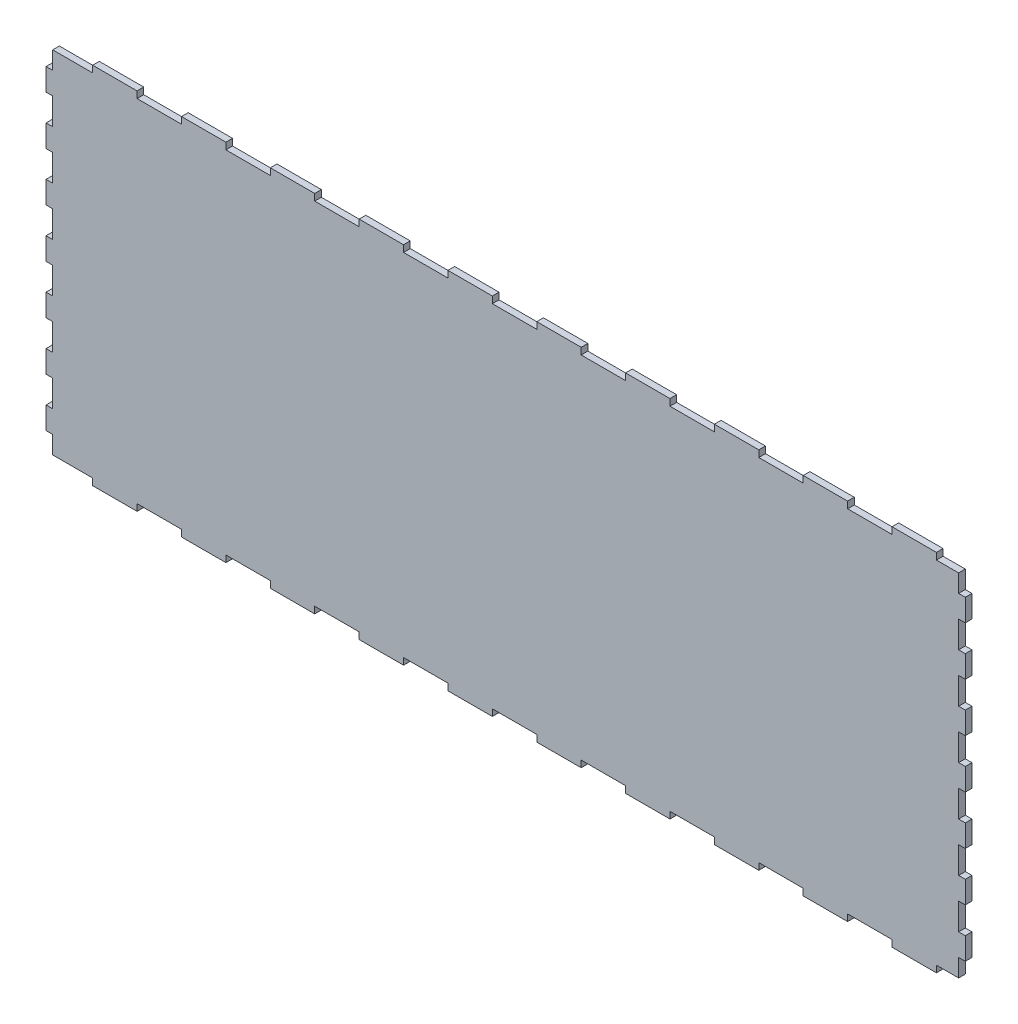
SolidWorks part; units mm, degrees
material "birch 3mm plywood"
ref_plane "Front Plane" through (0, 0, 0) normal (0, 0, 1) x (1, 0, 0)
ref_plane "Top Plane" through (0, 0, 0) normal (0, 1, 0) x (1, 0, 0)
ref_plane "Right Plane" through (0, 0, 0) normal (1, 0, 0) x (0, 0, -1)
sketch "Sketch1" plane through (0, 0, 152) normal (0, 0, 1) x (1, 0, 0)
  line L1 (-207, 82) -> (207, 82)
  line L2 (-207, 82) -> (-207, -82)
  line L3 (-207, -82) -> (207, -82)
  line L4 (207, 82) -> (207, -82)
  line L12 (200, -75) -> (-200, -75) construction
  line L13 (200, 75) -> (200, -75) construction
  line L14 (-200, -75) -> (-200, 75) construction
  line L15 (-200, 75) -> (200, 75) construction
  line L26 (-200, 0) -> (200, 0) construction
  line L31 (-200, 0) -> (200, 0) construction
  point P14 (0, 0)
  point P15 (0, 0)
  point P32 (-47.5, -25.9413)
  point P35 (256.981, -145.9413)
  point P38 (10.8894, 25.9413)
  point P51 (10.8894, -25.9413)
  point P54 (256.981, 145.9413)
  dimension "D1" = 7
  dimension "D2" = 7
  dimension "D3" = 7
  dimension "D4" = 7
  dimension "D5" = 150
  dimension "D6" = 400
extrude "Boss-Extrude1" add sketch "Sketch1" along normal blind 3
sketch "Sketch2" plane through (-207, 0, 0) normal (-1, 0, 0) x (0, 0, 1)
  line L7 (155, -82) -> (152, -82)
  line L8 (152, -82) -> (152, -71)
  line L9 (152, 82) -> (155, 82)
  line L10 (155, 82) -> (155, 71)
  line L11 (152, -61) -> (152, -49)
  line L12 (155, -71) -> (155, -82)
  line L13 (155, -49) -> (155, -61)
  line L14 (152, -39) -> (152, -27)
  line L15 (152, -17) -> (152, -5)
  line L16 (155, -27) -> (155, -39)
  line L17 (155, -5) -> (155, -17)
  line L18 (152, 5) -> (152, 17)
  line L19 (152, 27) -> (152, 39)
  line L20 (155, 17) -> (155, 5)
  line L21 (155, 39) -> (155, 27)
  line L22 (152, 49) -> (152, 61)
  line L23 (152, 71) -> (152, 82)
  line L24 (155, 61) -> (155, 49)
  line L76 (67, 82) -> (57, 82)
  line L77 (57, 82) -> (57, 79)
  line L78 (57, 79) -> (45, 79)
  line L79 (45, 79) -> (45, 82)
  line L80 (45, 82) -> (35, 82)
  line L81 (35, 82) -> (35, 79)
  line L82 (35, 79) -> (23, 79)
  line L83 (23, 79) -> (23, 82)
  line L84 (23, 82) -> (16, 82)
  line L85 (16, 82) -> (16, -82)
  line L86 (16, -82) -> (23, -82)
  line L87 (23, -82) -> (23, -79)
  line L88 (23, -79) -> (35, -79)
  line L89 (35, -79) -> (35, -82)
  line L90 (35, -82) -> (45, -82)
  line L91 (45, -82) -> (45, -79)
  line L92 (45, -79) -> (57, -79)
  line L93 (57, -79) -> (57, -82)
  line L94 (57, -82) -> (67, -82)
  line L95 (67, -82) -> (67, -79)
  line L96 (67, -79) -> (79, -79)
  line L97 (79, -79) -> (79, -82)
  line L98 (79, -82) -> (89, -82)
  line L99 (89, -82) -> (89, -79)
  line L100 (89, -79) -> (101, -79)
  line L101 (101, -79) -> (101, -82)
  line L102 (101, -82) -> (111, -82)
  line L103 (133, -82) -> (133, -79)
  line L104 (133, -79) -> (145, -79)
  line L105 (145, -79) -> (145, -82)
  line L106 (145, -82) -> (155, -82)
  line L107 (155, -82) -> (155, -71)
  line L108 (155, -71) -> (152, -71)
  line L109 (152, -71) -> (152, -61)
  line L110 (152, -61) -> (155, -61)
  line L111 (155, -61) -> (155, -49)
  line L112 (155, -49) -> (152, -49)
  line L113 (152, -49) -> (152, -39)
  line L114 (152, -39) -> (155, -39)
  line L115 (155, -39) -> (155, -27)
  line L116 (155, -27) -> (152, -27)
  line L117 (152, -27) -> (152, -17)
  line L118 (152, -17) -> (155, -17)
  line L119 (155, -17) -> (155, -5)
  line L120 (155, -5) -> (152, -5)
  line L121 (152, -5) -> (152, 5)
  line L122 (152, 5) -> (155, 5)
  line L123 (155, 5) -> (155, 17)
  line L124 (155, 17) -> (152, 17)
  line L125 (152, 17) -> (152, 27)
  line L126 (152, 27) -> (155, 27)
  line L127 (155, 27) -> (155, 39)
  line L128 (155, 39) -> (152, 39)
  line L129 (152, 39) -> (152, 49)
  line L130 (152, 49) -> (155, 49)
  line L131 (155, 49) -> (155, 61)
  line L132 (155, 61) -> (152, 61)
  line L133 (152, 61) -> (152, 71)
  line L134 (152, 71) -> (155, 71)
  line L135 (155, 71) -> (155, 82)
  line L136 (155, 82) -> (145, 82)
  line L137 (145, 82) -> (145, 79)
  line L138 (145, 79) -> (133, 79)
  line L139 (133, 79) -> (133, 82)
  line L140 (133, 82) -> (123, 82)
  line L141 (123, 82) -> (123, 79)
  line L142 (123, 79) -> (111, 79)
  line L143 (111, 79) -> (111, 82)
  line L144 (111, 82) -> (101, 82)
  line L145 (101, 82) -> (101, 79)
  line L146 (101, 79) -> (89, 79)
  line L147 (89, 79) -> (89, 82)
  line L148 (89, 82) -> (79, 82)
  line L149 (79, 82) -> (79, 79)
  line L150 (79, 79) -> (67, 79)
  line L151 (67, 79) -> (67, 82)
  line L184 (155, -71) -> (152, -71)
  line L186 (152, -61) -> (155, -61)
  line L188 (155, -49) -> (152, -49)
  line L190 (152, -39) -> (155, -39)
  line L192 (155, -27) -> (152, -27)
  line L194 (152, -17) -> (155, -17)
  line L196 (155, -5) -> (152, -5)
  line L198 (152, 5) -> (155, 5)
  line L200 (155, 17) -> (152, 17)
  line L202 (152, 27) -> (155, 27)
  line L204 (155, 39) -> (152, 39)
  line L206 (152, 49) -> (155, 49)
  line L208 (155, 61) -> (152, 61)
  line L210 (152, 71) -> (155, 71)
  line L565 (111, -82) -> (111, -79)
  line L567 (111, -79) -> (123, -79)
  line L569 (123, -79) -> (123, -82)
  line L571 (123, -82) -> (133, -82)
  dimension "D1" = 0
extrude "Cut-Extrude1" cut sketch "Sketch2" against normal blind 3
mirror "Mirror1" about plane through (0, 0, 0) normal (1, 0, 0) of "Cut-Extrude1"
sketch "Sketch3" plane through (0, 82, 0) normal (0, 1, 0) x (1, 0, 0)
  line L92 (174, -152) -> (194, -152)
  line L93 (194, -152) -> (194, -155)
  line L94 (194, -155) -> (204, -155)
  line L95 (204, -155) -> (204, -145)
  line L96 (204, -145) -> (207, -145)
  line L97 (207, -145) -> (207, -133)
  line L98 (207, -133) -> (204, -133)
  line L99 (204, -133) -> (204, -123)
  line L100 (204, -123) -> (207, -123)
  line L101 (207, -123) -> (207, -111)
  line L102 (207, -111) -> (204, -111)
  line L103 (204, -111) -> (204, -101)
  line L104 (204, -101) -> (207, -101)
  line L105 (207, -101) -> (207, -89)
  line L106 (207, -89) -> (204, -89)
  line L107 (204, -89) -> (204, -79)
  line L108 (204, -79) -> (207, -79)
  line L109 (207, -79) -> (207, -67)
  line L110 (207, -67) -> (204, -67)
  line L111 (204, -67) -> (204, -57)
  line L112 (204, -57) -> (207, -57)
  line L113 (207, -57) -> (207, -45)
  line L114 (207, -45) -> (204, -45)
  line L115 (204, -45) -> (204, -35)
  line L116 (204, -35) -> (207, -35)
  line L117 (207, -35) -> (207, -23)
  line L118 (207, -23) -> (204, -23)
  line L119 (204, -23) -> (204, -16)
  line L120 (204, -16) -> (-204, -16)
  line L121 (-204, -16) -> (-204, -23)
  line L122 (-204, -23) -> (-207, -23)
  line L123 (-207, -23) -> (-207, -35)
  line L124 (-207, -35) -> (-204, -35)
  line L125 (-204, -35) -> (-204, -45)
  line L126 (-204, -45) -> (-207, -45)
  line L127 (-207, -45) -> (-207, -57)
  line L128 (-207, -57) -> (-204, -57)
  line L129 (-204, -57) -> (-204, -67)
  line L130 (-204, -67) -> (-207, -67)
  line L131 (-207, -67) -> (-207, -79)
  line L132 (-207, -79) -> (-204, -79)
  line L133 (-204, -79) -> (-204, -89)
  line L134 (-204, -89) -> (-207, -89)
  line L135 (-207, -89) -> (-207, -101)
  line L136 (-207, -101) -> (-204, -101)
  line L137 (-204, -101) -> (-204, -111)
  line L138 (-204, -111) -> (-207, -111)
  line L139 (-207, -111) -> (-207, -123)
  line L140 (-207, -123) -> (-204, -123)
  line L141 (-204, -123) -> (-204, -133)
  line L142 (-204, -133) -> (-207, -133)
  line L143 (-207, -133) -> (-207, -145)
  line L144 (-207, -145) -> (-204, -145)
  line L145 (-204, -145) -> (-204, -155)
  line L146 (-204, -155) -> (-186, -155)
  line L147 (-186, -155) -> (-186, -152)
  line L148 (-186, -152) -> (-166, -152)
  line L149 (-166, -152) -> (-166, -155)
  line L150 (-166, -155) -> (-146, -155)
  line L151 (-146, -155) -> (-146, -152)
  line L152 (-146, -152) -> (-126, -152)
  line L153 (-126, -152) -> (-126, -155)
  line L154 (-126, -155) -> (-106, -155)
  line L155 (-106, -155) -> (-106, -152)
  line L156 (-106, -152) -> (-86, -152)
  line L157 (-86, -152) -> (-86, -155)
  line L158 (-86, -155) -> (-66, -155)
  line L159 (-66, -155) -> (-66, -152)
  line L160 (-66, -152) -> (-46, -152)
  line L161 (-46, -152) -> (-46, -155)
  line L162 (-46, -155) -> (-26, -155)
  line L163 (-26, -155) -> (-26, -152)
  line L164 (-26, -152) -> (-6, -152)
  line L165 (-6, -152) -> (-6, -155)
  line L166 (-6, -155) -> (14, -155)
  line L167 (14, -155) -> (14, -152)
  line L168 (14, -152) -> (34, -152)
  line L169 (34, -152) -> (34, -155)
  line L170 (34, -155) -> (54, -155)
  line L171 (54, -155) -> (54, -152)
  line L172 (54, -152) -> (74, -152)
  line L173 (74, -152) -> (74, -155)
  line L174 (74, -155) -> (94, -155)
  line L175 (94, -155) -> (94, -152)
  line L176 (94, -152) -> (114, -152)
  line L177 (114, -152) -> (114, -155)
  line L178 (114, -155) -> (134, -155)
  line L179 (134, -155) -> (134, -152)
  line L180 (134, -152) -> (154, -152)
  line L181 (154, -152) -> (154, -155)
  line L182 (154, -155) -> (174, -155)
  line L183 (174, -155) -> (174, -152)
  line L184 (174, -152) -> (194, -152)
  line L185 (194, -152) -> (194, -155)
  line L186 (194, -155) -> (204, -155)
  line L187 (204, -155) -> (204, -145)
  line L188 (204, -145) -> (207, -145)
  line L189 (207, -145) -> (207, -133)
  line L190 (207, -133) -> (204, -133)
  line L191 (204, -133) -> (204, -123)
  line L192 (204, -123) -> (207, -123)
  line L193 (207, -123) -> (207, -111)
  line L194 (207, -111) -> (204, -111)
  line L195 (204, -111) -> (204, -101)
  line L196 (204, -101) -> (207, -101)
  line L197 (207, -101) -> (207, -89)
  line L198 (207, -89) -> (204, -89)
  line L199 (204, -89) -> (204, -79)
  line L200 (204, -79) -> (207, -79)
  line L201 (207, -79) -> (207, -67)
  line L202 (207, -67) -> (204, -67)
  line L203 (204, -67) -> (204, -57)
  line L204 (204, -57) -> (207, -57)
  line L205 (207, -57) -> (207, -45)
  line L206 (207, -45) -> (204, -45)
  line L207 (204, -45) -> (204, -35)
  line L208 (204, -35) -> (207, -35)
  line L209 (207, -35) -> (207, -23)
  line L210 (207, -23) -> (204, -23)
  line L211 (204, -23) -> (204, -16)
  line L212 (204, -16) -> (-204, -16)
  line L213 (-204, -16) -> (-204, -23)
  line L214 (-204, -23) -> (-207, -23)
  line L215 (-207, -23) -> (-207, -35)
  line L216 (-207, -35) -> (-204, -35)
  line L217 (-204, -35) -> (-204, -45)
  line L218 (-204, -45) -> (-207, -45)
  line L219 (-207, -45) -> (-207, -57)
  line L220 (-207, -57) -> (-204, -57)
  line L221 (-204, -57) -> (-204, -67)
  line L222 (-204, -67) -> (-207, -67)
  line L223 (-207, -67) -> (-207, -79)
  line L224 (-207, -79) -> (-204, -79)
  line L225 (-204, -79) -> (-204, -89)
  line L226 (-204, -89) -> (-207, -89)
  line L227 (-207, -89) -> (-207, -101)
  line L228 (-207, -101) -> (-204, -101)
  line L229 (-204, -101) -> (-204, -111)
  line L230 (-204, -111) -> (-207, -111)
  line L231 (-207, -111) -> (-207, -123)
  line L232 (-207, -123) -> (-204, -123)
  line L233 (-204, -123) -> (-204, -133)
  line L234 (-204, -133) -> (-207, -133)
  line L235 (-207, -133) -> (-207, -145)
  line L236 (-207, -145) -> (-204, -145)
  line L237 (-204, -145) -> (-204, -155)
  line L238 (-204, -155) -> (-186, -155)
  line L239 (-186, -155) -> (-186, -152)
  line L240 (-186, -152) -> (-166, -152)
  line L241 (-166, -152) -> (-166, -155)
  line L242 (-166, -155) -> (-146, -155)
  line L243 (-146, -155) -> (-146, -152)
  line L244 (-146, -152) -> (-126, -152)
  line L245 (-126, -152) -> (-126, -155)
  line L246 (-126, -155) -> (-106, -155)
  line L247 (-106, -155) -> (-106, -152)
  line L248 (-106, -152) -> (-86, -152)
  line L249 (-86, -152) -> (-86, -155)
  line L250 (-86, -155) -> (-66, -155)
  line L251 (-66, -155) -> (-66, -152)
  line L252 (-66, -152) -> (-46, -152)
  line L253 (-46, -152) -> (-46, -155)
  line L254 (-46, -155) -> (-26, -155)
  line L255 (-26, -155) -> (-26, -152)
  line L256 (-26, -152) -> (-6, -152)
  line L257 (-6, -152) -> (-6, -155)
  line L258 (-6, -155) -> (14, -155)
  line L259 (14, -155) -> (14, -152)
  line L260 (14, -152) -> (34, -152)
  line L261 (34, -152) -> (34, -155)
  line L262 (34, -155) -> (54, -155)
  line L263 (54, -155) -> (54, -152)
  line L264 (54, -152) -> (74, -152)
  line L265 (74, -152) -> (74, -155)
  line L266 (74, -155) -> (94, -155)
  line L267 (94, -155) -> (94, -152)
  line L268 (94, -152) -> (114, -152)
  line L269 (114, -152) -> (114, -155)
  line L270 (114, -155) -> (134, -155)
  line L271 (134, -155) -> (134, -152)
  line L272 (134, -152) -> (154, -152)
  line L273 (154, -152) -> (154, -155)
  line L274 (154, -155) -> (174, -155)
  line L275 (174, -155) -> (174, -152)
  dimension "D1" = 0
extrude "Cut-Extrude2" cut sketch "Sketch3" against normal blind 3
mirror "Mirror2" about plane through (0, 0, 0) normal (0, 1, 0) of "Cut-Extrude2"
